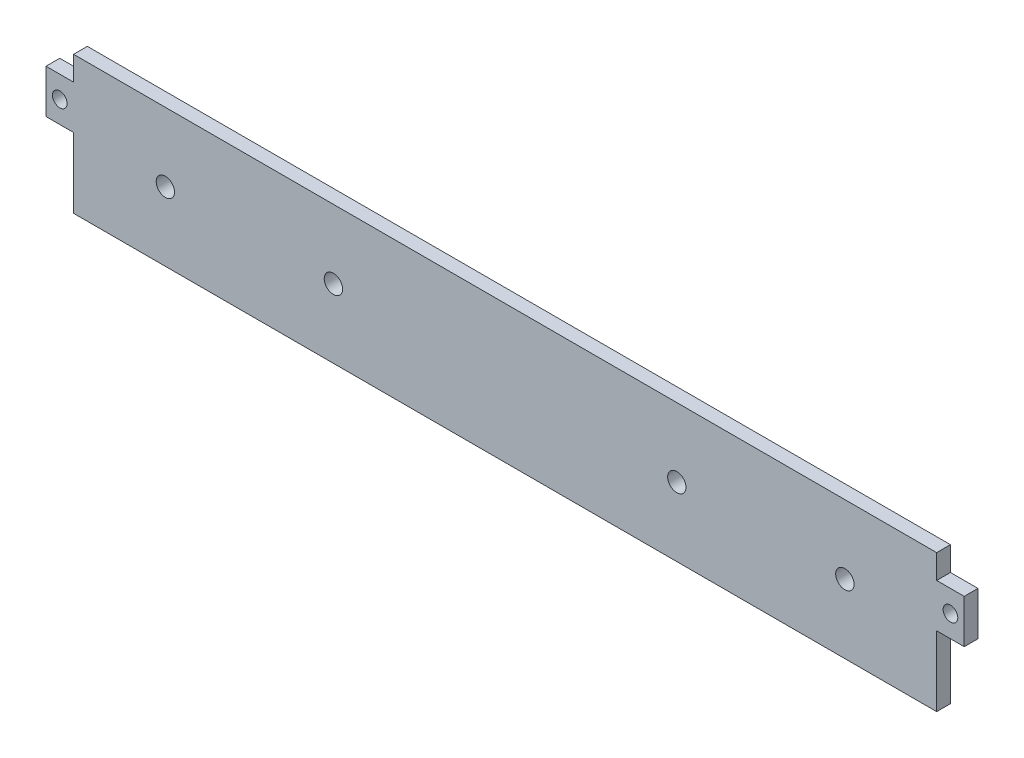
SolidWorks part; units mm, degrees
ref_plane "Plano frontal" through (0, 0, 0) normal (0, 0, 1) x (1, 0, 0)
ref_plane "Plano superior" through (0, 0, 0) normal (0, 1, 0) x (1, 0, 0)
ref_plane "Plano direito" through (0, 0, 0) normal (1, 0, 0) x (0, 0, -1)
sketch "Esboço1" plane through (0, 0, 0) normal (0, 0, 1) x (1, 0, 0)
  line L0 (-94, 0.25) -> (-94, -15)
  line L1 (-94, 15) -> (94, 15)
  line L2 (-94, 15) -> (-94, 9.75)
  line L3 (-94, -15) -> (94, -15)
  line L4 (94, 15) -> (94, 9.75)
  line L5 (-94, 15) -> (94, -15) construction
  line L6 (-94, -15) -> (94, 15) construction
  line L7 (-94, 9.75) -> (-100, 9.75)
  line L8 (0, 15) -> (0, -15) construction
  line L9 (-94, 0.25) -> (-100, 0.25)
  line L10 (-100, 9.75) -> (-100, 0.25)
  line L11 (94, 9.75) -> (100, 9.75)
  line L12 (94, 0.25) -> (100, 0.25)
  line L13 (100, 9.75) -> (100, 0.25)
  line L14 (94, 0.25) -> (94, -15)
  line L15 (-100, 9.75) -> (-94, 0.25) construction
  circle A0 centre (-97, 5) radius 1.6
  circle A1 centre (97, 5) radius 1.6
  circle A2 centre (-74, 0) radius 2
  circle A3 centre (-37.4, 0) radius 2
  circle A4 centre (37.4, 0) radius 2
  circle A5 centre (74, 0) radius 2
  point P0 (0, 0)
  point P24 (0, 0)
  dimension "D6" = 3.2
  dimension "D7" = 4
  dimension "D1" = 188
  dimension "D2" = 30
  dimension "D3" = 9.5
  dimension "D4" = 6
  dimension "D5" = 5.25
  dimension "D8" = 36.6
  dimension "D9" = 15
  dimension "D10" = 20
extrude "Ressalto-extrusão1" add sketch "Esboço1" along normal blind 3
